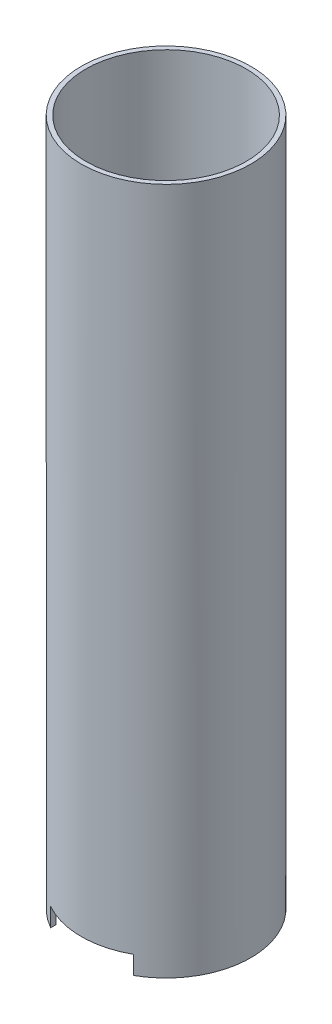
SolidWorks part; units mm, degrees
ref_plane "Front Plane" through (0, 0, 0) normal (0, 0, 1) x (1, 0, 0)
ref_plane "Top Plane" through (0, 0, 0) normal (0, 1, 0) x (1, 0, 0)
ref_plane "Right Plane" through (0, 0, 0) normal (1, 0, 0) x (0, 0, -1)
sketch "Sketch1" plane through (0, 0, 0) normal (0, 1, 0) x (1, 0, 0)
  line L0 (-17.5, 0) -> (17.5, 0) construction
  line L1 (0, 17.5) -> (0, 15) construction
  line L2 (-9.0139, 15) -> (9.0139, 15)
  line L3 (-9.0139, -15) -> (9.0139, -15)
  line L4 (-9.0139, 15) -> (-9.0139, 16.1555)
  line L5 (9.0139, 15) -> (9.0139, 16.1555)
  line L6 (-9.0139, -15) -> (-9.0139, -16.1555)
  line L7 (9.0139, -15) -> (9.0139, -16.1555)
  circle A0 centre (0, 0) radius 18.5
  circle A1 centre (0, 0) radius 17.5
  circle A2 centre (0, 0) radius 5.5562 construction
  dimension "D1" = 37
  dimension "D2" = 35
  dimension "D4" = 11.1125
  dimension "D3" = 2.5
extrude "Shell" add sketch "Sketch1" along normal blind 150 contours A1 L4 A0 L6 | A1 L6 A0 L7 | A1 L5 A0 L4 | A1 L7 A0 L5 region at (-17.8367, 0, 0) region at (-8.8302, 0, -15.5777) region at (9.3506, 0, -15.5777) region at (0, 0, 17.6836)
ref_plane "Plane3" through (0, 120, 0) normal (0, 1, 0) x (1, 0, 0)
sketch "Sketch8" plane through (0, 120, 0) normal (0, 1, 0) x (1, 0, 0)
  line L0 (0, -12) -> (0, 0) construction
  circle A0 centre (0, 0) radius 17.5
  circle A2 centre (0, -12) radius 3.5
  circle A3 centre (0, 0) radius 5.5562
  dimension "D1" = 12
  dimension "D2" = 7
  dimension "D3" = 35
  dimension "D4" = 11.1125
extrude "RodAligner" add sketch "Sketch8" along normal mid plane 2
extrude "Cut-Extrude1" cut sketch "Sketch1<7>" along normal blind 4 contours A1 L5 A0 L4 | A1 L6 A0 L7 region at (-8.8302, 0, -15.5777) region at (0, 0, 17.6836)
sketch "Sketch1<7>" plane through (0, 0, 0) normal (0, 1, 0) x (1, 0, 0) same geometry as "Sketch1"
